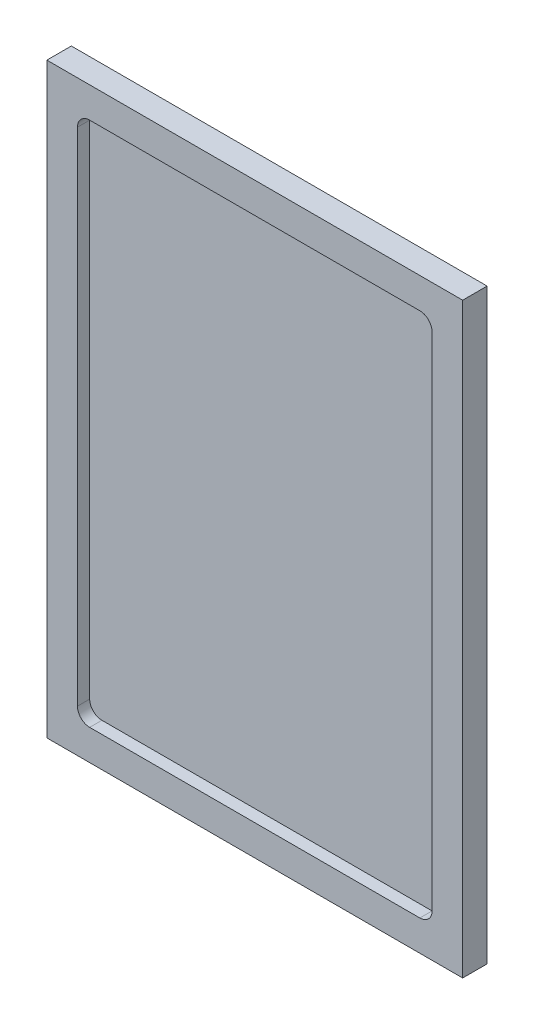
SolidWorks part; units mm, degrees
ref_plane "Front Plane" through (0, 0, 0) normal (0, 0, 1) x (1, 0, 0)
ref_plane "Top Plane" through (0, 0, 0) normal (0, 1, 0) x (1, 0, 0)
ref_plane "Right Plane" through (0, 0, 0) normal (1, 0, 0) x (0, 0, -1)
sketch "Sketch1" plane through (0, 0, 0) normal (0, 0, 1) x (1, 0, 0)
  line L1 (107.95, -152.4) -> (-107.95, -152.4)
  line L2 (107.95, -152.4) -> (107.95, 152.4)
  line L3 (107.95, 152.4) -> (-107.95, 152.4)
  line L4 (-107.95, -152.4) -> (-107.95, 152.4)
  line L5 (107.95, -152.4) -> (-107.95, 152.4) construction
  line L6 (107.95, 152.4) -> (-107.95, -152.4) construction
  point P0 (0, 0)
  dimension "D1" = 215.9
  dimension "D2" = 304.8
extrude "Boss-Extrude1" add sketch "Sketch1" along normal blind 12.7
sketch "Sketch2" plane through (0, 0, 12.7) normal (0, 0, 1) x (1, 0, 0)
  line L0 (-107.95, 152.4) -> (-107.95, -152.4) construction
  line L1 (85.725, -136.525) -> (-85.725, -136.525)
  line L2 (92.075, -130.175) -> (92.075, 130.175)
  line L3 (85.725, 136.525) -> (-85.725, 136.525)
  line L4 (-92.075, -130.175) -> (-92.075, 130.175)
  line L5 (92.075, -136.525) -> (-92.075, 136.525) construction
  line L6 (92.075, 136.525) -> (-92.075, -136.525) construction
  line L7 (107.95, 152.4) -> (-107.95, 152.4) construction
  arc A0 (-85.725, -136.525) -> (-92.075, -130.175) centre (-85.725, -130.175) cw
  arc A1 (85.725, -136.525) -> (92.075, -130.175) centre (85.725, -130.175) ccw
  arc A2 (92.075, 130.175) -> (85.725, 136.525) centre (85.725, 130.175) ccw
  arc A3 (-85.725, 136.525) -> (-92.075, 130.175) centre (-85.725, 130.175) ccw
  point P0 (0, 0)
  dimension "D3" = 6.35
  dimension "D1" = 15.875
  dimension "D2" = 15.875
extrude "Cut-Extrude1" cut sketch "Sketch2" against normal blind 6.35
